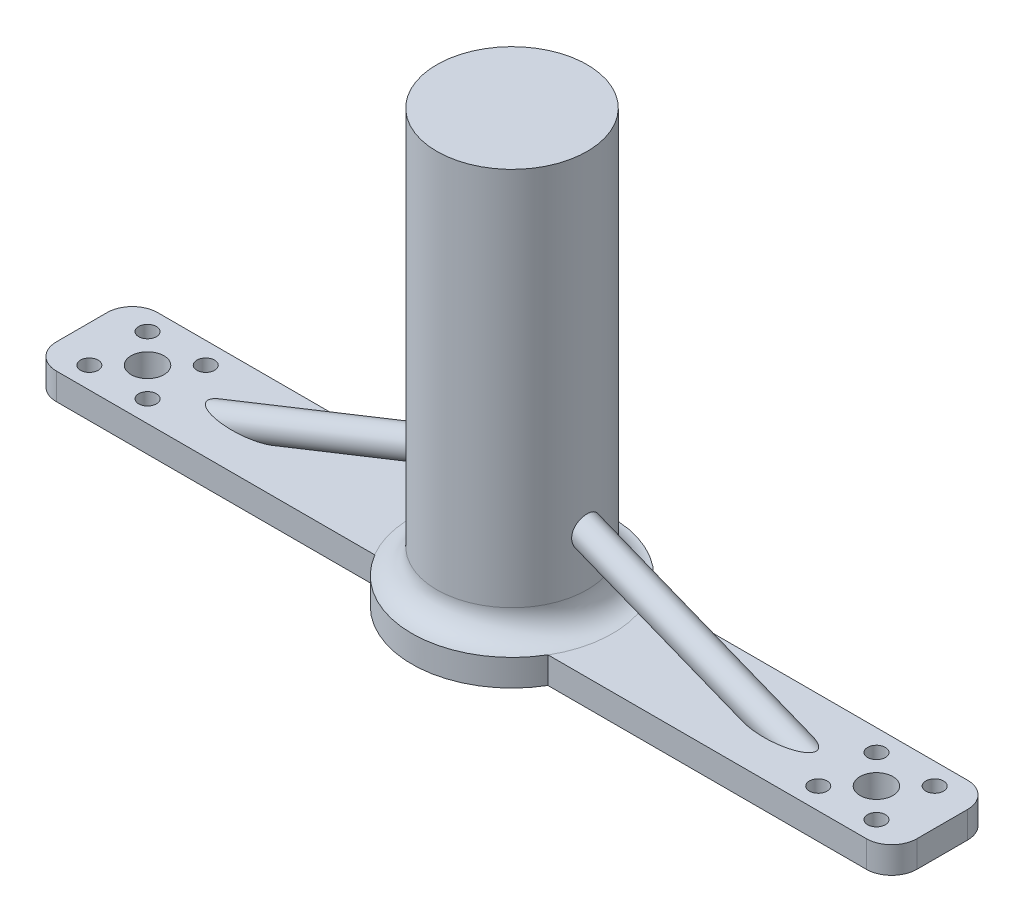
SolidWorks part; units mm, degrees
ref_plane "Front Plane" through (0, 0, 0) normal (0, 0, 1) x (1, 0, 0)
ref_plane "Top Plane" through (0, 0, 0) normal (0, 1, 0) x (1, 0, 0)
ref_plane "Right Plane" through (0, 0, 0) normal (1, 0, 0) x (0, 0, -1)
sketch "Sketch1" plane through (0, 0, 0) normal (0, 1, 0) x (1, 0, 0)
  line L0 (10.9105, 10) -> (17.0892, 10) construction
  line L1 (-85, -10) -> (-17.0892, -10)
  line L2 (-85, -10) -> (-85, 10)
  line L3 (-85, 10) -> (-17.0892, 10)
  line L4 (85, -10) -> (85, 10)
  line L5 (-85, -10) -> (85, 10) construction
  line L6 (-85, 10) -> (85, -10) construction
  line L7 (17.0892, 10) -> (85, 10)
  line L8 (-10.9105, 10) -> (10.9105, 10) construction
  line L9 (-17.0892, 10) -> (-10.9105, 10) construction
  line L10 (-17.0892, -10) -> (-10.9105, -10) construction
  line L11 (17.0892, -10) -> (85, -10)
  line L12 (-10.9105, -10) -> (10.9105, -10) construction
  line L13 (10.9105, -10) -> (17.0892, -10) construction
  circle A0 centre (0, 0) radius 14.8 construction
  arc A1 (-17.0892, -10) -> (17.0892, -10) centre (0, 0) ccw
  arc A2 (-17.0892, 10) -> (-19.6644, 2.3135) centre (0, 0) ccw construction
  arc A3 (-19.6644, 2.3135) -> (-19.6644, -2.3135) centre (0, 0) ccw construction
  arc A4 (-19.6644, -2.3135) -> (-17.0892, -10) centre (0, 0) ccw construction
  arc A5 (17.0892, -10) -> (19.6644, -2.3135) centre (0, 0) ccw construction
  arc A6 (17.0892, 10) -> (-17.0892, 10) centre (0, 0) ccw
  arc A7 (19.6644, -2.3135) -> (19.6644, 2.3135) centre (0, 0) ccw construction
  arc A8 (19.6644, 2.3135) -> (17.0892, 10) centre (0, 0) ccw construction
  point P0 (0, 0)
  dimension "D1" = 29.6
  dimension "D2" = 10
  dimension "D3" = 5
  dimension "D4" = 85
extrude "Boss-Extrude1" add sketch "Sketch1" along normal blind 5.25
sketch "Sketch3" plane through (0, 5.25, 0) normal (0, 1, 0) x (1, 0, 0)
  circle A0 centre (0, 0) radius 14.85
  dimension "D1" = 29.7
extrude "Boss-Extrude2" add sketch "Sketch3" along normal blind 80
sketch "Sketch4" plane through (0, 5.25, 0) normal (0, 1, 0) x (1, 0, 0)
  line L1 (-30, 5) -> (30, 5)
  line L2 (-30, 5) -> (-30, -5)
  line L3 (-30, -5) -> (30, -5)
  line L4 (30, 5) -> (30, -5)
  line L5 (-30, 5) -> (30, -5) construction
  line L6 (-30, -5) -> (30, 5) construction
  circle A0 centre (0, 0) radius 14.85 construction
  point P0 (0, 0)
  dimension "D1" = 10
  dimension "D2" = 30
sketch "Sketch2" plane through (0, 5.25, 0) normal (0, 1, 0) x (1, 0, 0)
  line L0 (0, 0) -> (0, 2.7485) construction
  line L3 (0, 0) -> (-72, 0) construction
  line L5 (-77.75, -5.75) -> (-66.25, -5.75) construction
  line L6 (-77.75, -5.75) -> (-77.75, 5.75) construction
  line L7 (-77.75, 5.75) -> (-66.25, 5.75) construction
  line L8 (-66.25, -5.75) -> (-66.25, 5.75) construction
  line L9 (-77.75, -5.75) -> (-66.25, 5.75) construction
  line L10 (-77.75, 5.75) -> (-66.25, -5.75) construction
  circle A0 centre (-77.75, 5.75) radius 1.75
  circle A1 centre (-66.25, 5.75) radius 1.75
  circle A2 centre (-66.25, -5.75) radius 1.75
  circle A3 centre (-77.75, -5.75) radius 1.75
  circle A4 centre (-72, 0) radius 63.5 construction
  circle A9 centre (77.75, -5.75) radius 1.75
  circle A10 centre (66.25, -5.75) radius 1.75
  circle A11 centre (77.75, 5.75) radius 1.75
  circle A12 centre (66.25, 5.75) radius 1.75
  circle A13 centre (-72, 0) radius 3.25
  circle A14 centre (72, 0) radius 3.25
  dimension "D1" = 3.5
  dimension "D3" = 127
  dimension "D5" = 6.5
  dimension "D2" = 11.5
  dimension "D4" = 72
extrude "Cut-Extrude1" cut sketch "Sketch2" against normal through all
ref_plane "Plane1" through (0, 0, 0) normal (0, 0, 1) x (1, 0, 0)
sketch "Sketch5" plane through (0, 0, 0) normal (0, 0, 1) x (1, 0, 0)
  line L0 (-14.85, 23.25) -> (-60.0774, 5.25)
  line L1 (-14.85, 85.25) -> (-14.85, 5.25) construction
  line L2 (-85, 5.25) -> (-17.0892, 5.25) construction
  line L3 (14.85, 5.25) -> (-14.85, 5.25) construction
  line L4 (-60.0774, 5.25) -> (-58.968, 2.4626)
  line L5 (-58.968, 2.4626) -> (-14.85, 20.0211)
  line L6 (-14.85, 20.0211) -> (-14.85, 23.25)
  dimension "D1" = 18
  dimension "D2" = 3
revolve "Revolve1" add sketch "Sketch5" angle 360 about L5
fillet "Fillet8" radius 5 4 edges at (85, 2.625, -10) (85, 2.625, 10) (-85, 2.625, -10) (-85, 2.625, 10)
ref_plane "Plane2" through (0, 0, 0) normal (-1, 0, 0) x (0, 0, 1)
mirror "Mirror1" about plane through (0, 0, 0) normal (-1, 0, 0) of "Revolve1"
fillet "Fillet9" radius 5 1 edges at (0, 5.25, 14.85)
